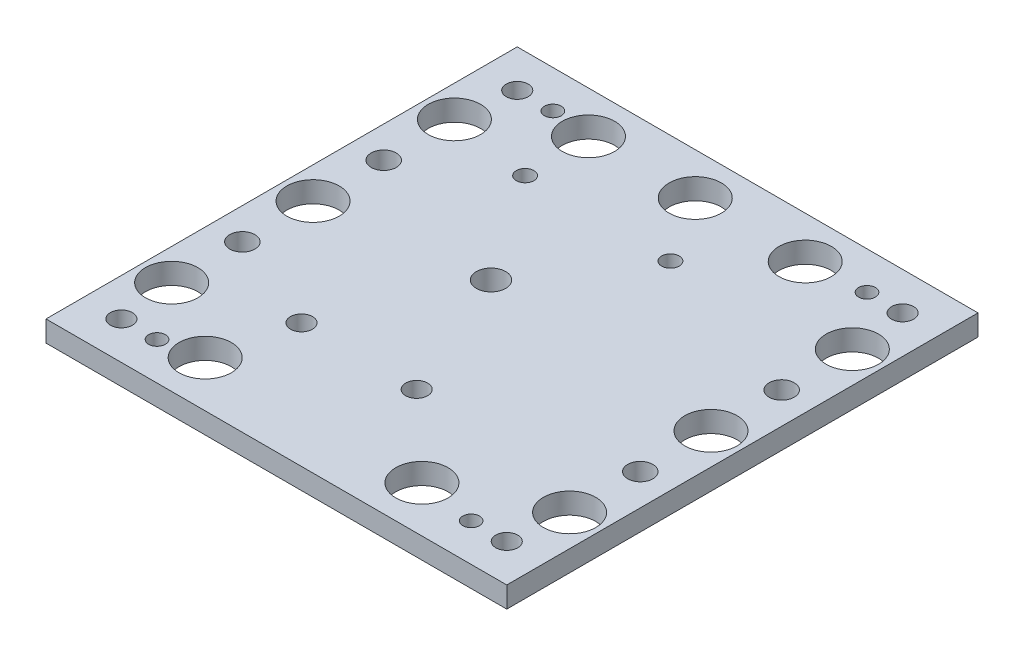
SolidWorks part; units mm, degrees
material "K110"
ref_plane "Front Plane" through (0, 0, 0) normal (0, 0, 1) x (1, 0, 0)
ref_plane "Top Plane" through (0, 0, 0) normal (0, 1, 0) x (1, 0, 0)
ref_plane "Right Plane" through (0, 0, 0) normal (1, 0, 0) x (0, 0, -1)
sketch "Sketch1" plane through (0, 0, 0) normal (0, 1, 0) x (1, 0, 0)
  line L1 (-110, -112.5) -> (110, -112.5)
  line L2 (-110, -112.5) -> (-110, 112.5)
  line L3 (-110, 112.5) -> (110, 112.5)
  line L4 (110, -112.5) -> (110, 112.5)
  line L5 (-110, -112.5) -> (110, 112.5) construction
  line L6 (-110, 112.5) -> (110, -112.5) construction
  point P0 (0, 0)
  dimension "D1" = 220
  dimension "D2" = 225
extrude "Boss-Extrude1" add sketch "Sketch1" along normal blind 10
sketch "Sketch3" plane through (0, 0, 0) normal (0, -1, 0) x (1, 0, 0)
  circle A0 centre (-19.87, -9.86) radius 7 construction
  circle A1 centre (-19.87, -9.86) radius 7
extrude "Cut-Extrude2" cut sketch "Sketch3" against normal up to next
hole_wizard "Ø8.0mm Dowel Hole1" positions "Sketch7" profile "Sketch5" hole size "Ø8.0" standard "ISO" end condition through all
sketch "Sketch7" plane through (0, 10, 0) normal (0, 1, 0) x (1, 0, 0)
  point P0 (75, -94.5)
  point P3 (-75, -94.5)
  point P6 (75, 94.5)
  point P10 (-75, 94.5)
sketch "Sketch5" plane through (75, 10, 94.5) normal (1, 0, 0) x (0, 0, 1)
  line L0 (0, 0) -> (0, 10)
  line L1 (0, 10) -> (4, 10)
  line L2 (4, 10) -> (4, 0)
  line L5 (4, 0) -> (0, 0)
  line L11 (0, -6.35) -> (0, 107.95) construction
  dimension "Thru Hole Dia." = 8
  dimension "Thru Hole Depth" = 10
hole_wizard "M10 Clearance Hole1" positions "Sketch10" profile "Sketch9" hole size "M10" standard "ISO" end condition through all
sketch "Sketch10" plane through (0, 10, 0) normal (0, 1, 0) x (1, 0, 0)
  point P0 (92, -94.5)
  point P3 (92, 94.5)
  point P6 (-92, 94.5)
  point P9 (-92, -94.5)
sketch "Sketch9" plane through (92, 10, 94.5) normal (1, 0, 0) x (0, 0, 1)
  line L0 (0, 0) -> (0, 10)
  line L1 (0, 10) -> (5.25, 10)
  line L2 (5.25, 10) -> (5.25, 0)
  line L5 (5.25, 0) -> (0, 0)
  line L11 (0, -6.35) -> (0, 107.95) construction
  dimension "Thru Hole Dia." = 10.5
  dimension "Thru Hole Depth" = 10
hole_wizard "M10 Clearance Hole2" positions "Sketch13" profile "Sketch12" hole size "M10" standard "ISO" end condition through all
sketch "Sketch13" plane through (0, 10, 0) normal (0, 1, 0) x (1, 0, 0)
  point P0 (7.63, -53.14)
  point P3 (-47.37, -53.14)
sketch "Sketch12" plane through (7.63, 10, 53.14) normal (1, 0, 0) x (0, 0, 1)
  line L0 (0, 0) -> (0, 10)
  line L1 (0, 10) -> (5.25, 10)
  line L2 (5.25, 10) -> (5.25, 0)
  line L5 (5.25, 0) -> (0, 0)
  line L11 (0, -6.35) -> (0, 107.95) construction
  dimension "Thru Hole Dia." = 10.5
  dimension "Thru Hole Depth" = 10
hole_wizard "M8 Clearance Hole1" positions "Sketch16" profile "Sketch15" hole size "M8" standard "ISO" end condition through all
sketch "Sketch16" plane through (0, 10, 0) normal (0, 1, 0) x (1, 0, 0)
  point P0 (15.13, 60.5)
  point P3 (-54.87, 61.13)
sketch "Sketch15" plane through (15.13, 10, -60.5) normal (1, 0, 0) x (0, 0, 1)
  line L0 (0, 0) -> (0, 10)
  line L1 (0, 10) -> (4.2, 10)
  line L2 (4.2, 10) -> (4.2, 0)
  line L5 (4.2, 0) -> (0, 0)
  line L11 (0, -6.35) -> (0, 107.95) construction
  dimension "Thru Hole Dia." = 8.4
  dimension "Thru Hole Depth" = 10
sketch "Sketch17" plane through (0, 10, 0) normal (0, 1, 0) x (1, 0, 0)
  circle A0 centre (-95, -67.5) radius 12.5 construction
  circle A1 centre (-95, 0) radius 12.5 construction
  circle A2 centre (-95, 67.5) radius 12.5 construction
  circle A3 centre (-56, -90.5) radius 12.5 construction
  circle A4 centre (47.5, -90.5) radius 12.5 construction
  circle A5 centre (95, -67.5) radius 12.5 construction
  circle A6 centre (95, 0) radius 12.5 construction
  circle A7 centre (95, 67.5) radius 12.5 construction
  circle A8 centre (47.5, 92.5) radius 12.5 construction
  circle A9 centre (-5, 92.5) radius 12.5 construction
  circle A10 centre (-56, 92.5) radius 12.5 construction
  circle A11 centre (-95, -67.5) radius 12.5
  circle A12 centre (-95, 0) radius 12.5
  circle A13 centre (-95, 67.5) radius 12.5
  circle A14 centre (-56, -90.5) radius 12.5
  circle A15 centre (47.5, -90.5) radius 12.5
  circle A16 centre (95, -67.5) radius 12.5
  circle A17 centre (95, 0) radius 12.5
  circle A18 centre (95, 67.5) radius 12.5
  circle A19 centre (47.5, 92.5) radius 12.5
  circle A20 centre (-5, 92.5) radius 12.5
  circle A21 centre (-56, 92.5) radius 12.5
extrude "Cut-Extrude3" cut sketch "Sketch17" against normal up to next
hole_wizard "Ø12.0 (12) Diameter Hole1" positions "Sketch20" profile "Sketch19" hole size "Ø12.0" standard "ISO" end condition through all
sketch "Sketch20" plane through (0, 10, 0) normal (0, 1, 0) x (1, 0, 0)
  line L0 (-95, -67.5) -> (-95, 0) construction
  line L1 (-95, 0) -> (-95, 67.5) construction
  line L3 (95, -67.5) -> (95, 0) construction
  line L4 (95, 0) -> (95, 67.5) construction
  point P19 (-95, -33.75)
  point P21 (-95, 33.75)
  point P23 (95, 33.75)
  point P25 (95, -33.75)
sketch "Sketch19" plane through (95, 10, 33.75) normal (1, 0, 0) x (0, 0, 1)
  line L0 (0, 0) -> (0, 10)
  line L1 (0, 10) -> (6, 10)
  line L2 (6, 10) -> (6, 0)
  line L5 (6, 0) -> (0, 0)
  line L11 (0, -6.35) -> (0, 107.95) construction
  dimension "Thru Hole Dia." = 12
  dimension "Thru Hole Depth" = 10
